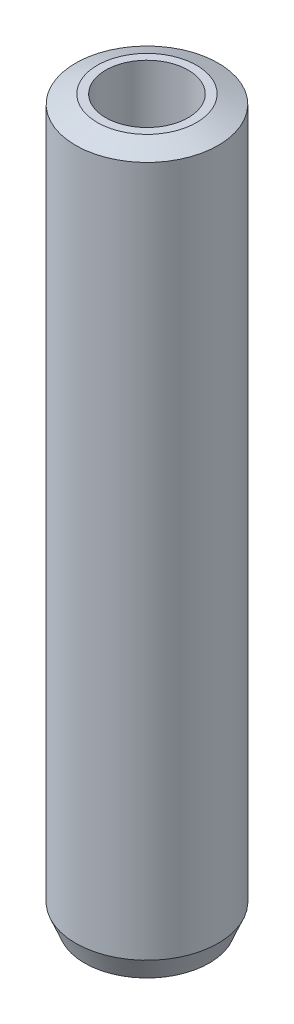
SolidWorks part; units mm, degrees
ref_plane "Front Plane" through (0, 0, 0) normal (0, 0, 1) x (1, 0, 0)
ref_plane "Top Plane" through (0, 0, 0) normal (0, 1, 0) x (1, 0, 0)
ref_plane "Right Plane" through (0, 0, 0) normal (1, 0, 0) x (0, 0, -1)
sketch "Sketch1" plane through (0, 0, 0) normal (0, 1, 0) x (1, 0, 0)
  circle A0 centre (0, 0) radius 47.5
  dimension "SHAFT_OD" = 95
extrude "Boss-Extrude1" add sketch "Sketch1" along normal blind 480.6303
sketch "Sketch2" plane through (0, 0, 0) normal (0, 1, 0) x (1, 0, 0)
  circle A0 centre (0, 0) radius 27.48
  dimension "BORE_D" = 54.96
extrude "Cut-Extrude1" cut sketch "Sketch2" along normal through all
chamfer "Chamfer1" distance 5.9603 angle 67.573 2 edges at (0, 480.6303, 47.5) (0, 0, 47.5) first distance on face at (0, 480.6303, 47.5) first distance on face at (0, 0, 27.48)
